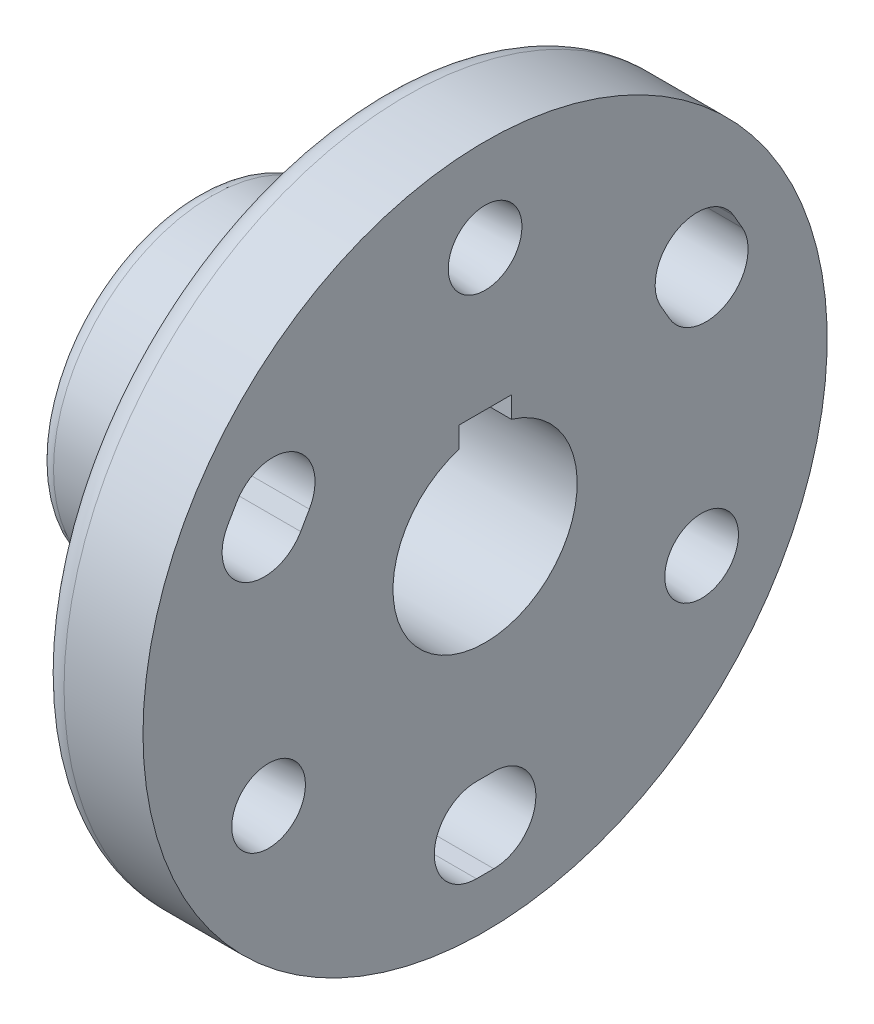
SolidWorks part; units mm, degrees
ref_plane "Front Plane" through (0, 0, 0) normal (0, 0, 1) x (1, 0, 0)
ref_plane "Top Plane" through (0, 0, 0) normal (0, 1, 0) x (1, 0, 0)
ref_plane "Right Plane" through (0, 0, 0) normal (1, 0, 0) x (0, 0, -1)
sketch "Sketch1" plane through (0, 0, 0) normal (0, 0, 1) x (1, 0, 0)
  line L0 (-55, 0) -> (0, 0)
  line L1 (0, 0) -> (0, 65)
  line L2 (0, 65) -> (-15, 65)
  line L3 (-20, 60) -> (-20, 38)
  line L4 (-28, 30) -> (-52, 30)
  line L5 (-55, 27) -> (-55, 0)
  arc A0 (-20, 38) -> (-28, 30) centre (-28, 38) cw
  arc A1 (-15, 65) -> (-20, 60) centre (-15, 60) ccw
  arc A2 (-52, 30) -> (-55, 27) centre (-52, 27) ccw
  point P11 (-20, 65)
  dimension "D4" = 8
  dimension "D5" = 5
  dimension "D6" = 3
  dimension "D1" = 20
  dimension "D2" = 65
  dimension "D3" = 55
  dimension "D7" = 30
revolve "Revolve1" add sketch "Sketch1" angle 360 about L0
sketch "Sketch2" plane through (-55, 0, 0) normal (-1, 0, 0) x (0, 0, 1)
  circle A0 centre (0, 0) radius 17.5
  dimension "D1" = 35
extrude "Cut-Extrude1" cut sketch "Sketch2" against normal through all
sketch "Sketch3" plane through (0, 0, 0) normal (1, 0, 0) x (0, 0, -1)
  line L1 (-5, 14.2) -> (5, 14.2)
  line L2 (-5, 14.2) -> (-5, 20.8)
  line L3 (-5, 20.8) -> (5, 20.8)
  line L4 (5, 14.2) -> (5, 20.8)
  line L5 (-5, 14.2) -> (5, 20.8) construction
  line L6 (-5, 20.8) -> (5, 14.2) construction
  circle A0 centre (0, 0) radius 17.5 construction
  point P0 (0, 17.5)
  dimension "D1" = 10
  dimension "D2" = 3.3
extrude "Cut-Extrude2" cut sketch "Sketch3" against normal through all
ref_plane "Plane2" through (0, -30, 0) normal (0, -1, 0) x (-1, 0, 0)
sketch "Sketch4" plane through (0, -30, 0) normal (0, -1, 0) x (-1, 0, 0)
  circle A0 centre (40.2298, 0) radius 4
  dimension "D1" = 8
extrude "Cut-Extrude3" cut sketch "Sketch4" against normal blind 10
cosmetic thread "Cosmetic Thread1" parameters "D2"=10
sketch "Sketch5" plane through (0, 0, 0) normal (1, 0, 0) x (0, 0, -1)
  line L0 (-1.65, -47.5) -> (1.65, -47.5) construction
  line L1 (-1.65, -39.5) -> (1.65, -39.5)
  line L2 (-1.65, -55.5) -> (1.65, -55.5)
  line L3 (-40.3112, 25.1789) -> (-41.9612, 22.3211) construction
  line L4 (-33.383, 21.1789) -> (-35.033, 18.3211)
  line L5 (-47.2394, 29.1789) -> (-48.8894, 26.3211)
  line L6 (41.9612, 22.3211) -> (40.3112, 25.1789) construction
  line L7 (35.033, 18.3211) -> (33.383, 21.1789)
  line L8 (48.8894, 26.3211) -> (47.2394, 29.1789)
  arc A0 (-1.65, -39.5) -> (-1.65, -55.5) centre (-1.65, -47.5) ccw
  arc A1 (1.65, -55.5) -> (1.65, -39.5) centre (1.65, -47.5) ccw
  circle A2 centre (0, 0) radius 47.5
  arc A3 (-33.383, 21.1789) -> (-47.2394, 29.1789) centre (-40.3112, 25.1789) ccw
  arc A4 (-48.8894, 26.3211) -> (-35.033, 18.3211) centre (-41.9612, 22.3211) ccw
  arc A5 (35.033, 18.3211) -> (48.8894, 26.3211) centre (41.9612, 22.3211) ccw
  arc A6 (47.2394, 29.1789) -> (33.383, 21.1789) centre (40.3112, 25.1789) ccw
  circle A7 centre (0, 47.5) radius 7
  circle A8 centre (41.1362, -23.75) radius 7
  circle A9 centre (-41.1362, -23.75) radius 7
  point P2 (0, -47.5)
  point P15 (-41.1362, 23.75)
  point P22 (41.1362, 23.75)
  point P27 (0, 0)
  point P33 (0, 0)
  dimension "D2" = 8
  dimension "D3" = 95
  dimension "D5" = 14
  dimension "D1" = 3.3
  dimension "D4" = 3
  dimension "D6" = 3
extrude "Cut-Extrude4" cut sketch "Sketch5" against normal through all contours L5 A4 A2 A3 | A2 A4 L4 A3 | A2 A6 L7 A5 | L8 A6 A2 A5 | A0 A2 A1 L1 | A2 A0 L2 A1 | L4 A4 L5 A3 region at (0, -43.8102, 0) region at (0, -50.8405, 0) region at (0, 25.4203, 44.0292) region at (0, 21.9051, 37.9408) region at (0, 21.9051, -37.9408) region at (0, 25.4203, -44.0292)
extrude "Cut-Extrude5" cut sketch "Sketch5<3>" against normal through all draft 4.289 contours A2 A7 | A2 A7 | A2 A9 | A2 A9 | A2 A8 | A2 A8 region at (0, -25.188, 43.6269) region at (0, -22.2191, 38.4846) region at (0, -22.2191, -38.4846) region at (0, -25.188, -43.6269) region at (0, 50.3761, 0) region at (0, 44.4381, 0)
sketch "Sketch5<3>" plane through (0, 0, 0) normal (1, 0, 0) x (0, 0, -1) same geometry as "Sketch5"
